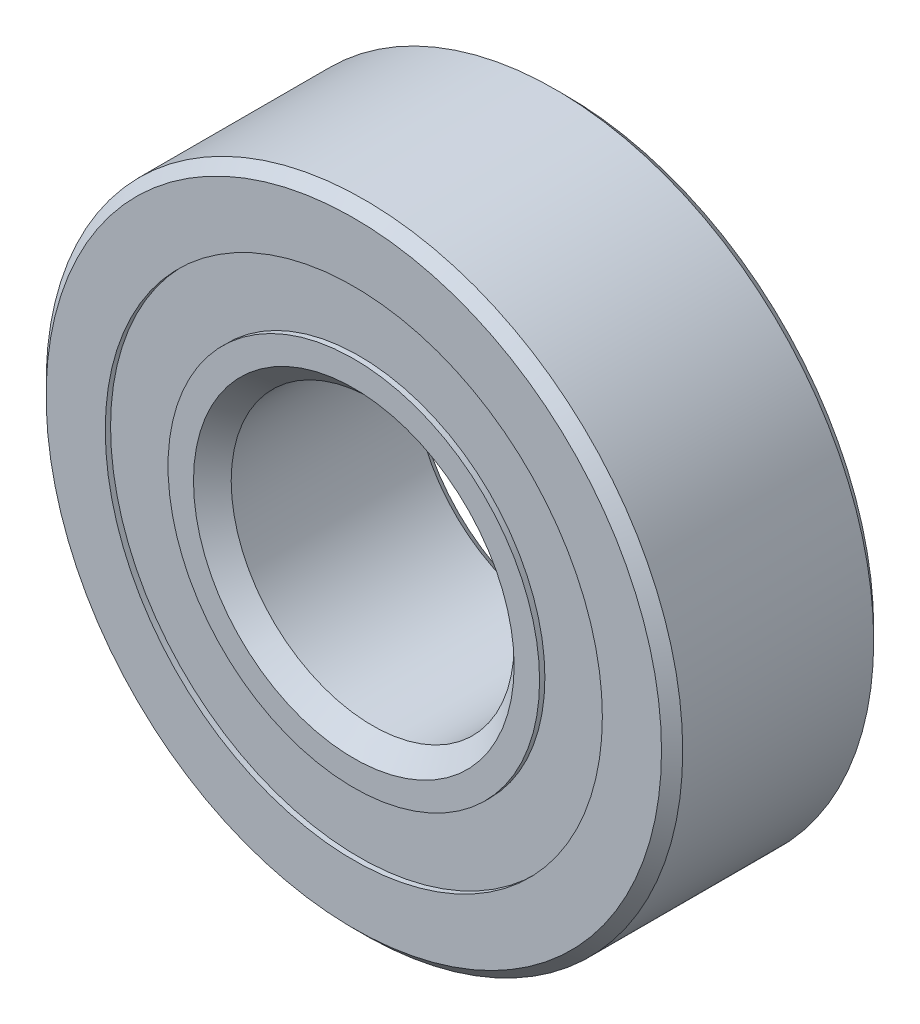
SolidWorks part; units mm, degrees
material "AISI 1020 Steel, Cold Rolled"
ref_plane "Front Plane" through (0, 0, 0) normal (0, 0, 1) x (1, 0, 0)
ref_plane "Top Plane" through (0, 0, 0) normal (0, 1, 0) x (1, 0, 0)
ref_plane "Right Plane" through (0, 0, 0) normal (1, 0, 0) x (0, 0, -1)
sketch "Sketch1" plane through (0, 0, 0) normal (1, 0, 0) x (0, 0, -1)
  line L0 (-4.7625, 0) -> (4.7625, 0) construction
  line L1 (0, 14.2875) -> (0, -14.2875) construction
  line L2 (4.2863, 14.2875) -> (-4.2863, 14.2875)
  line L3 (-4.2863, 14.2875) -> (-4.7625, 13.8113)
  line L4 (-4.7625, 13.8113) -> (-4.7625, 11.1561)
  line L5 (-4.7625, 11.1561) -> (-2.1167, 11.1561)
  line L6 (4.7625, 11.1561) -> (2.1167, 11.1561)
  line L7 (4.7625, 13.8113) -> (4.7625, 11.1561)
  line L8 (4.2863, 14.2875) -> (4.7625, 13.8113)
  line L9 (0, 14.2875) -> (0, 10.3187) construction
  line L10 (0, 10.3187) -> (0, 6.35) construction
  arc A0 (-2.1167, 11.1561) -> (2.1167, 11.1561) centre (0, 10.3187) cw
  point P14 (0, 6.35)
  dimension "Width" = 9.525
  dimension "OD" = 28.575
  dimension "D1" = 45
  dimension "D2" = 0.4763
  dimension "D3" = 4.2333
  dimension "D4" = 0.8374
revolve "Revolve1" add sketch "Sketch1" angle 360 about L0
sketch "Sketch2" plane through (0, 0, 0) normal (1, 0, 0) x (0, 0, -1)
  line L0 (-4.5244, 9.4814) -> (-2.1167, 9.4814)
  line L1 (-4.7625, 13.8113) -> (-4.7625, -13.8113) construction
  line L2 (-4.7625, 8.3388) -> (-4.5244, 8.3388) construction
  line L3 (-4.5244, 8.1007) -> (-3.6199, 7.1962)
  line L4 (-3.6199, 7.1962) -> (0, 7.1962)
  line L5 (0, 14.2875) -> (0, -14.2875) construction
  line L6 (0, 7.1962) -> (0, 8.0425)
  line L7 (0, 8.0425) -> (0, 6.35) construction
  line L8 (-4.7625, 9.4814) -> (-4.7625, 7.1962) construction
  line L9 (-4.7625, 7.1962) -> (-3.6199, 7.1962) construction
  line L10 (-4.5244, 9.4814) -> (-4.5244, 8.1007)
  line L11 (-4.5244, 9.4814) -> (-4.5244, 14.0494) construction
  line L12 (-4.2863, 14.2875) -> (-4.7625, 13.8113) construction
  arc A0 (-2.1167, 9.4814) -> (0, 8.0425) centre (0, 10.3187) ccw
  arc A1 (2.1167, 11.1561) -> (-2.1167, 11.1561) centre (0, 10.3187) ccw construction
  circle A2 centre (0, 10.3187) radius 2.2763 construction
  dimension "D1" = 45
revolve "Revolve2" [suppressed] add sketch "Sketch2" angle 360 about L0
sketch "Sketch3" plane through (0, 0, 0) normal (1, 0, 0) x (0, 0, -1)
  line L0 (-4.5244, 8.1007) -> (-3.6199, 7.1962)
  line L1 (-3.6199, 7.1962) -> (0, 7.1962)
  line L2 (0, 7.1962) -> (0, 8.0425)
  line L3 (-4.7625, 8.3388) -> (-4.7625, 7.1962)
  line L4 (-4.7625, 9.4814) -> (-4.7625, 7.1962) construction
  line L5 (-4.7625, 7.1962) -> (-3.9163, 6.35)
  line L6 (-3.9163, 6.35) -> (4.2863, 6.35)
  line L7 (4.2863, 14.2875) -> (4.2863, -14.2875) construction
  line L8 (4.2863, 6.35) -> (4.7625, 6.8262)
  line L9 (4.7625, -13.8113) -> (4.7625, 13.8113) construction
  line L10 (4.7625, 6.8262) -> (4.7625, 9.4814)
  line L11 (4.7625, 9.4814) -> (2.1167, 9.4814)
  line L12 (-4.7625, 8.3388) -> (-4.5244, 8.3388)
  line L13 (4.2863, 14.2875) -> (4.7625, 13.8113) construction
  line L14 (-4.5244, 8.3388) -> (-4.5244, 8.1007)
  circle A0 centre (0, 10.3187) radius 2.2763 construction
  arc A1 (2.1167, 9.4814) -> (0, 8.0425) centre (0, 10.3187) cw
revolve "Revolve3" add sketch "Sketch3" angle 360 about L0
sketch "Sketch4" plane through (0, 0, 0) normal (1, 0, 0) x (0, 0, -1)
  line L0 (-2.2763, 10.3187) -> (2.2763, 10.3187)
  circle A1 centre (0, 10.3187) radius 2.2763 construction
  arc A2 (-2.2763, 10.3187) -> (2.2763, 10.3187) centre (0, 10.3187) cw
  arc A3 (2.1167, 11.1561) -> (-2.1167, 11.1561) centre (0, 10.3187) ccw construction
revolve "Revolve4" add sketch "Sketch4" angle 360 about L0
ref_axis "Axis1" through (0, 0, -4.7625) along (0, 0, 1)
pattern_circular "CirPattern1" count 10 every 36 about axis through (0, 0, -4.7625) along (0, 0, 1) of bodies 104
sketch "Sketch5" plane through (0, 0, 0) normal (1, 0, 0) x (0, 0, -1)
  line L0 (-4.7625, 11.1561) -> (-2.1167, 11.1561) construction
  line L1 (-4.5244, 11.1561) -> (-2.2763, 11.1561)
  line L2 (-4.5244, 11.1561) -> (-4.5244, 8.3388)
  line L3 (-4.5244, 8.3388) -> (-2.2763, 8.3388)
  line L4 (-2.2763, 11.1561) -> (-2.2763, 8.3388)
  line L6 (-4.2863, 14.2875) -> (-4.7625, 13.8113) construction
  line L7 (0, 14.2875) -> (0, 6.35) construction
  line L8 (4.5244, 8.3388) -> (2.2763, 8.3388)
  line L9 (2.2763, 11.1561) -> (2.2763, 8.3388)
  line L10 (4.5244, 11.1561) -> (2.2763, 11.1561)
  line L11 (4.5244, 11.1561) -> (4.5244, 8.3388)
  circle A0 centre (0, 10.3187) radius 2.2763 construction
  point P10 (-4.5244, 14.0494)
revolve "Revolve5" add sketch "Sketch5" angle 360 about L0
equation "\"D2@Sketch1\" = \"Width@Sketch1\"*.05"
equation "\"D3@Sketch1\" = \"Width@Sketch1\"/2.25"
equation "\"D4@Sketch1\" = (((\"OD@Sketch1\"-\"Width@Sketch1\")/2)/3.25)/3.5"
equation "\"D2@CirPattern1\" = 360/\"Balls@CirPattern1\""
